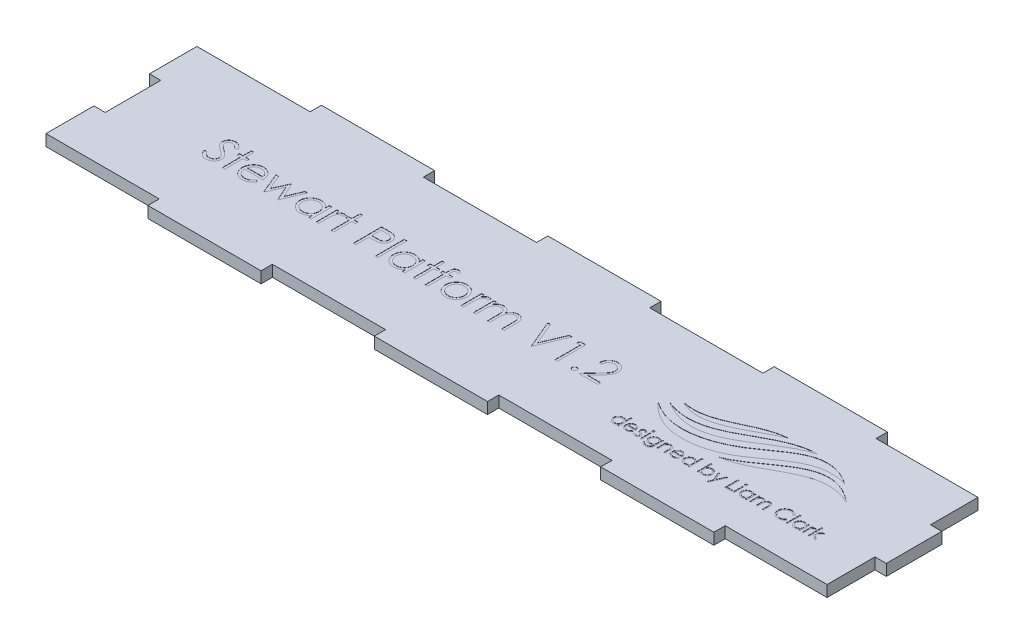
SolidWorks part; units mm, degrees
ref_plane "Front Plane" through (0, 0, 0) normal (0, 0, 1) x (1, 0, 0)
ref_plane "Top Plane" through (0, 0, 0) normal (0, 1, 0) x (1, 0, 0)
ref_plane "Right Plane" through (0, 0, 0) normal (1, 0, 0) x (0, 0, -1)
sketch "Sketch1" plane through (0, 0, 0) normal (0, 1, 0) x (1, 0, 0)
  line L1 (210, -46) -> (-210, -46)
  line L2 (210, -46) -> (210, 46)
  line L3 (210, 46) -> (-210, 46)
  line L4 (-210, -46) -> (-210, 46)
  line L5 (210, -46) -> (-210, 46) construction
  line L6 (210, 46) -> (-210, -46) construction
  point P0 (0, 0)
  dimension "D1" = 92
  dimension "D2" = 420
extrude "Boss-Extrude1" add sketch "Sketch1" along normal blind 6
sketch "Sketch2" plane through (0, 6, 0) normal (0, 1, 0) x (1, 0, 0)
  line L0 (210, 46) -> (-210, 46) construction
  line L1 (-210, 46) -> (-150, 46)
  line L2 (-210, 46) -> (-210, 40)
  line L3 (-210, 40) -> (-150, 40)
  line L4 (-150, 46) -> (-150, 40)
  line L5 (210, 0) -> (-210, 0) construction
  line L6 (-90, 46) -> (-90, 40)
  line L7 (-90, 46) -> (-30, 46)
  line L8 (-30, 46) -> (-30, 40)
  line L9 (-90, 40) -> (-30, 40)
  line L10 (30, 46) -> (30, 40)
  line L11 (30, 46) -> (90, 46)
  line L12 (90, 46) -> (90, 40)
  line L13 (30, 40) -> (90, 40)
  line L14 (-90, -40) -> (-90, -46)
  line L15 (-90, -40) -> (-30, -40)
  line L16 (-30, -40) -> (-30, -46)
  line L17 (-90, -46) -> (-30, -46)
  line L18 (30, -40) -> (30, -46)
  line L19 (30, -40) -> (90, -40)
  line L20 (90, -40) -> (90, -46)
  line L21 (30, -46) -> (90, -46)
  line L22 (-210, -40) -> (-210, -46)
  line L23 (-210, -40) -> (-150, -40)
  line L24 (-150, -40) -> (-150, -46)
  line L25 (-210, -46) -> (-150, -46)
  line L26 (210, -46) -> (210, 46) construction
  line L31 (-210, 46) -> (-210, -46) construction
  line L32 (150, 46) -> (150, 40)
  line L33 (150, 46) -> (210, 46)
  line L34 (210, 46) -> (210, 40)
  line L35 (150, 40) -> (210, 40)
  line L36 (150, -40) -> (150, -46)
  line L37 (150, -40) -> (210, -40)
  line L38 (210, -40) -> (210, -46)
  line L39 (150, -46) -> (210, -46)
  point P6 (-210, 43)
  dimension "D1" = 6
  dimension "D2" = 60
  dimension "D3" = 60
  dimension "D4" = 4
  dimension "D5" = 2
extrude "Cut-Extrude1" cut sketch "Sketch2" against normal through all
sketch "Sketch4" plane through (0, 6, 0) normal (0, 1, 0) x (1, 0, 0)
  line L0 (-210, 40) -> (-210, -40) construction
  line L1 (-210, 14.8279) -> (-204, 14.8279)
  line L2 (-210, 14.8279) -> (-210, -14.6242)
  line L3 (-210, -14.6242) -> (-204, -14.6242)
  line L4 (-204, 14.8279) -> (-204, -14.6242)
  line L5 (210, -40) -> (210, 40) construction
  line L6 (210, 44) -> (204, 44)
  line L7 (210, 44) -> (210, 14.8279)
  line L8 (210, 14.8279) -> (204, 14.8279)
  line L9 (204, 44) -> (204, 14.8279)
  line L10 (210, -44) -> (204, -44)
  line L11 (210, -44) -> (210, -14.6242)
  line L12 (210, -14.6242) -> (204, -14.6242)
  line L13 (204, -44) -> (204, -14.6242)
  dimension "D1" = 6
extrude "Cut-Extrude2" cut sketch "Sketch4" against normal through all
sketch "Sketch6" [suppressed] plane through (0, 6, 0) normal (0, 1, 0) x (1, 0, 0)
  line L0 (-150, -40) -> (-210, -40) construction
  line L14 (-93, -40) -> (-3, -40) construction
  line L15 (-93, -40) -> (-93, -19) construction
  line L16 (-93, -19) -> (-3, -19) construction
  line L17 (-3, -40) -> (-3, -19) construction
  line L18 (7, -40) -> (97, -40) construction
  line L19 (-96, -40) -> (0, -40) construction
  line L20 (-96, -40) -> (-96, -4) construction
  line L21 (-96, -4) -> (0, -4) construction
  line L170 (0, -40) -> (0, -4) construction
  line L171 (7, -40) -> (7, -19) construction
  line L172 (7, -19) -> (97, -19) construction
  line L173 (97, -40) -> (97, -19) construction
  line L174 (4, -40) -> (100, -40) construction
  line L175 (4, -40) -> (4, -4) construction
  line L176 (4, -4) -> (100, -4) construction
  line L177 (100, -40) -> (100, -4) construction
  line L178 (107, -40) -> (197, -40) construction
  line L179 (107, -40) -> (107, -19) construction
  line L180 (107, -19) -> (197, -19) construction
  line L181 (197, -40) -> (197, -19) construction
  line L182 (104, -40) -> (200, -40) construction
  line L183 (104, -40) -> (104, -4) construction
  line L184 (104, -4) -> (200, -4) construction
  line L185 (200, -40) -> (200, -4) construction
  line L188 (204, -14.6242) -> (204, -40) construction
  circle A10 centre (-93, -19) radius 2
  circle A11 centre (-3, -19) radius 2
  circle A12 centre (7, -19) radius 2
  circle A13 centre (97, -19) radius 2
  circle A14 centre (107, -19) radius 2
  circle A15 centre (197, -19) radius 2
  point P12 (-48, -4)
  point P13 (-48, -19)
  dimension "D4" = 96
  dimension "D5" = 36
  dimension "D3" = 4
  dimension "D1" = 90
  dimension "D2" = 21
  dimension "D6" = 3
  dimension "D7" = 4
  dimension "D8" = 4
extrude "Cut-Extrude4" [suppressed] cut sketch "Sketch6" against normal through all
sketch "Sketch7" plane through (0, 6, 0) normal (0, 1, 0) x (1, 0, 0)
  spline S0 degree 3 poles (171.3644, 2.9041) (149.1407, 21.5097) (134.8367, -3.6597) (116.6334, -10.2554) knots 0 0 0 0 1 1 1 1
  spline S1 degree 3 poles (171.3644, 2.9041) (149.4646, 13.3802) (136.0003, -7.5908) (116.6334, -10.2554) knots 0 0 0 0 1 1 1 1
  spline S2 degree 3 poles (162.7253, 10.8278) (143.1108, 16.5369) (123.5303, -12.8755) (86.3571, -14.1609) (75.3762, -0.8054) knots 0 0 0 0 0.516039 1 1 1 1
  spline S3 degree 3 poles (162.7253, 10.8278) (143.6265, 23.6489) (123.0567, -4.3635) (87.9253, -10.4996) (75.3762, -0.8054) knots 0 0 0 0 0.521405 1 1 1 1
  spline S4 degree 3 poles (142.09, 17.4582) (120.5651, 11.5313) (105.0269, -14.3308) (78.5591, 1.9413) knots 0 0 0 0 1 1 1 1
  spline S5 degree 3 poles (142.09, 17.4582) (118.744, 17.2291) (104.4879, -8.4421) (78.5591, 1.9413) knots 0 0 0 0 1 1 1 1
  spline S6 degree 3 poles (126.7097, 16.9429) (113.3406, 11.8174) (97.8584, -2.6356) (82.1577, 5.6639) knots 0 0 0 0 1 1 1 1
  spline S7 degree 3 poles (126.7097, 16.9429) (110.86, 15.9088) (98.9912, 1.6673) (82.1577, 5.6639) knots 0 0 0 0 1 1 1 1
  text T0 "designed by Liam Clark\r\n" font "Century Gothic" height 7
  text T1 "Stewart Platform V1.2" font "Century Gothic" height 15
extrude "Cut-Extrude5" cut sketch "Sketch7" against normal blind 0.1
sketch "Sketch8" [suppressed] plane through (0, 6, 0) normal (0, 1, 0) x (1, 0, 0)
  line L0 (-196, -40) -> (-106, -40) construction
  line L1 (-196, -40) -> (-196, -19) construction
  line L2 (-196, -19) -> (-106, -19) construction
  line L3 (-106, -40) -> (-106, -19) construction
  line L4 (-199, -40) -> (-103, -40) construction
  line L5 (-199, -40) -> (-199, -4) construction
  line L6 (-199, -4) -> (-103, -4) construction
  line L7 (-103, -40) -> (-103, -4) construction
  line L8 (-150, -40) -> (-210, -40) construction
  line L9 (-96, -40) -> (-6, -40) construction
  line L10 (-96, -40) -> (-96, -19) construction
  line L11 (-96, -19) -> (-6, -19) construction
  line L12 (-6, -40) -> (-6, -19) construction
  line L13 (-99, -40) -> (-3, -40) construction
  line L14 (-99, -40) -> (-99, -4) construction
  line L15 (-99, -4) -> (-3, -4) construction
  line L16 (-3, -40) -> (-3, -4) construction
  line L17 (4, -40) -> (94, -40) construction
  line L18 (4, -40) -> (4, -19) construction
  line L19 (4, -19) -> (94, -19) construction
  line L20 (94, -40) -> (94, -19) construction
  line L21 (1, -40) -> (97, -40) construction
  line L22 (1, -40) -> (1, -4) construction
  line L23 (1, -4) -> (97, -4) construction
  line L24 (97, -40) -> (97, -4) construction
  line L25 (-204, -14.6242) -> (-204, 14.8279) construction
  circle A0 centre (-196, -19) radius 2
  circle A1 centre (-106, -19) radius 2
  circle A2 centre (-96, -19) radius 2
  circle A3 centre (-6, -19) radius 2
  circle A4 centre (4, -19) radius 2
  circle A5 centre (94, -19) radius 2
  point P10 (-151, -4)
  point P11 (-151, -19)
  dimension "D3" = 4
  dimension "D1" = 90
  dimension "D2" = 21
  dimension "D4" = 96
  dimension "D5" = 36
  dimension "D7" = 5
  dimension "D8" = 4
  dimension "D6" = 3
extrude "Cut-Extrude6" [suppressed] cut sketch "Sketch8" against normal through all
sketch "Sketch10" [suppressed] plane through (0, 6, 0) normal (0, 1, 0) x (1, 0, 0)
  line L0 (-204, -14.6242) -> (-204, 14.8279) construction
  line L1 (-204, 40) -> (-124, 40) construction
  line L2 (-204, 40) -> (-204, -40) construction
  line L3 (-204, -40) -> (-124, -40) construction
  line L4 (-124, 40) -> (-124, -40) construction
  line L5 (-210, 40) -> (-150, 40) construction
  line L6 (-164, 40) -> (-164, -40) construction
  line L7 (-124, 0) -> (-204, 0) construction
  line L8 (-165, 9.9499) -> (-169.9668, 35.5021)
  line L9 (-200, -36) -> (-128, -36) construction
  line L10 (-200, -36) -> (-200, 36) construction
  line L11 (-200, 36) -> (-128, 36) construction
  line L12 (-128, -36) -> (-128, 36) construction
  line L13 (-200, -36) -> (-128, 36) construction
  line L14 (-200, 36) -> (-128, -36) construction
  line L15 (-163, 9.9499) -> (-158.0332, 35.5021)
  line L16 (-159.2685, 8.8098) -> (-144.9013, 30.5162)
  line L17 (-161.1162, 9.5752) -> (-155.9266, 35.083)
  line L18 (-156.2573, 6.3285) -> (-134.6771, 20.8846)
  line L19 (-157.6715, 7.7427) -> (-143.1154, 29.3229)
  line L20 (-154.4248, 2.8838) -> (-128.917, 8.0734)
  line L21 (-155.1902, 4.7315) -> (-133.4838, 19.0987)
  line L22 (-154.0501, -1) -> (-128.4979, -5.9668)
  line L23 (-154.0501, 1) -> (-128.4979, 5.9668)
  line L24 (-155.1902, -4.7315) -> (-133.4838, -19.0987)
  line L25 (-154.4248, -2.8838) -> (-128.917, -8.0734)
  line L26 (-157.6715, -7.7427) -> (-143.1154, -29.3229)
  line L27 (-156.2573, -6.3285) -> (-134.6771, -20.8846)
  line L28 (-161.1162, -9.5752) -> (-155.9266, -35.083)
  line L29 (-159.2685, -8.8098) -> (-144.9013, -30.5162)
  line L30 (-165, -9.9499) -> (-169.9668, -35.5021)
  line L31 (-163, -9.9499) -> (-158.0332, -35.5021)
  line L32 (-168.7315, -8.8098) -> (-183.0987, -30.5162)
  line L33 (-166.8838, -9.5752) -> (-172.0734, -35.083)
  line L34 (-171.7427, -6.3285) -> (-193.3229, -20.8846)
  line L35 (-170.3285, -7.7427) -> (-184.8846, -29.3229)
  line L36 (-173.5752, -2.8838) -> (-199.083, -8.0734)
  line L37 (-172.8098, -4.7315) -> (-194.5162, -19.0987)
  line L38 (-173.9499, 1) -> (-199.5021, 5.9668)
  line L39 (-173.9499, -1) -> (-199.5021, -5.9668)
  line L40 (-172.8098, 4.7315) -> (-194.5162, 19.0987)
  line L41 (-173.5752, 2.8838) -> (-199.083, 8.0734)
  line L42 (-170.3285, 7.7427) -> (-184.8846, 29.3229)
  line L43 (-171.7427, 6.3285) -> (-193.3229, 20.8846)
  line L44 (-166.8838, 9.5752) -> (-172.0734, 35.083)
  line L45 (-168.7315, 8.8098) -> (-183.0987, 30.5162)
  circle A0 centre (-200, -36) radius 2.25
  circle A1 centre (-128, -36) radius 2.25
  circle A2 centre (-128, 36) radius 2.25
  circle A3 centre (-200, 36) radius 2.25
  arc A5 (-169.9668, 35.5021) -> (-158.0332, 35.5021) centre (-164, 0) cw
  arc A6 (-163, 9.9499) -> (-165, 9.9499) centre (-164, 0) ccw
  arc A7 (-155.9266, 35.083) -> (-144.9013, 30.5162) centre (-164, 0) cw
  arc A8 (-159.2685, 8.8098) -> (-161.1162, 9.5752) centre (-164, 0) ccw
  arc A9 (-143.1154, 29.3229) -> (-134.6771, 20.8846) centre (-164, 0) cw
  arc A10 (-156.2573, 6.3285) -> (-157.6715, 7.7427) centre (-164, 0) ccw
  arc A11 (-133.4838, 19.0987) -> (-128.917, 8.0734) centre (-164, 0) cw
  arc A12 (-154.4248, 2.8838) -> (-155.1902, 4.7315) centre (-164, 0) ccw
  arc A13 (-128.4979, 5.9668) -> (-128.4979, -5.9668) centre (-164, 0) cw
  arc A14 (-154.0501, -1) -> (-154.0501, 1) centre (-164, 0) ccw
  arc A15 (-128.917, -8.0734) -> (-133.4838, -19.0987) centre (-164, 0) cw
  arc A16 (-155.1902, -4.7315) -> (-154.4248, -2.8838) centre (-164, 0) ccw
  arc A17 (-134.6771, -20.8846) -> (-143.1154, -29.3229) centre (-164, 0) cw
  arc A18 (-157.6715, -7.7427) -> (-156.2573, -6.3285) centre (-164, 0) ccw
  arc A19 (-144.9013, -30.5162) -> (-155.9266, -35.083) centre (-164, 0) cw
  arc A20 (-161.1162, -9.5752) -> (-159.2685, -8.8098) centre (-164, 0) ccw
  arc A21 (-158.0332, -35.5021) -> (-169.9668, -35.5021) centre (-164, 0) cw
  arc A22 (-165, -9.9499) -> (-163, -9.9499) centre (-164, 0) ccw
  arc A23 (-172.0734, -35.083) -> (-183.0987, -30.5162) centre (-164, 0) cw
  arc A24 (-168.7315, -8.8098) -> (-166.8838, -9.5752) centre (-164, 0) ccw
  arc A25 (-184.8846, -29.3229) -> (-193.3229, -20.8846) centre (-164, 0) cw
  arc A26 (-171.7427, -6.3285) -> (-170.3285, -7.7427) centre (-164, 0) ccw
  arc A27 (-194.5162, -19.0987) -> (-199.083, -8.0734) centre (-164, 0) cw
  arc A28 (-173.5752, -2.8838) -> (-172.8098, -4.7315) centre (-164, 0) ccw
  arc A29 (-199.5021, -5.9668) -> (-199.5021, 5.9668) centre (-164, 0) cw
  arc A30 (-173.9499, 1) -> (-173.9499, -1) centre (-164, 0) ccw
  arc A31 (-199.083, 8.0734) -> (-194.5162, 19.0987) centre (-164, 0) cw
  arc A32 (-172.8098, 4.7315) -> (-173.5752, 2.8838) centre (-164, 0) ccw
  arc A33 (-193.3229, 20.8846) -> (-184.8846, 29.3229) centre (-164, 0) cw
  arc A34 (-170.3285, 7.7427) -> (-171.7427, 6.3285) centre (-164, 0) ccw
  arc A35 (-183.0987, 30.5162) -> (-172.0734, 35.083) centre (-164, 0) cw
  arc A36 (-166.8838, 9.5752) -> (-168.7315, 8.8098) centre (-164, 0) ccw
  point P12 (-164, 0)
  point P89 (-164, 0)
  dimension "D3" = 4.5
  dimension "D4" = 36
  dimension "D5" = 10
  dimension "D7" = 2
  dimension "D1" = 80
  dimension "D2" = 72
  dimension "D6" = 22
extrude "Cut-Extrude10" [suppressed] cut sketch "Sketch10" against normal through all
mirror "Mirror1" [suppressed] about plane through (0, 0, 0) normal (1, 0, 0)
sketch "Sketch9" [suppressed] plane through (0, 6, 0) normal (0, 1, 0) x (1, 0, 0)
  line L0 (-204, -14.6242) -> (-204, 14.8279) construction
  line L1 (-204, -4) -> (-133, -4) construction
  line L2 (-204, -4) -> (-204, -40) construction
  line L3 (-204, -40) -> (-133, -40) construction
  line L4 (-133, -4) -> (-133, -40) construction
  line L5 (-30, -40) -> (-90, -40) construction
  line L6 (0, 46) -> (0, -46) construction
  line L7 (30, 46) -> (-30, 46) construction
  line L8 (-30, -46) -> (30, -46) construction
  line L9 (204, -4) -> (204, -40) construction
  line L10 (204, -40) -> (133, -40) construction
  line L11 (133, -4) -> (133, -40) construction
  line L12 (204, -4) -> (133, -4) construction
  line L13 (90, -40) -> (30, -40) construction
  line L14 (-107.5, -40) -> (107.5, -40) construction
  line L15 (-107.5, -40) -> (-107.5, 12) construction
  line L16 (-107.5, 12) -> (107.5, 12) construction
  line L17 (107.5, -40) -> (107.5, 12) construction
  line L18 (14, 27) -> (-14, 27) construction
  line L19 (-14, 37) -> (14, 37)
  line L20 (-14, 37) -> (-14, 17)
  line L21 (-14, 17) -> (14, 17)
  line L22 (14, 37) -> (14, 17)
  line L23 (-14, 37) -> (14, 17) construction
  line L24 (-14, 17) -> (14, 37) construction
  line L25 (0, 37) -> (0, 17) construction
  circle A0 centre (82.5, -27) radius 2.25
  circle A1 centre (-34.5, -27) radius 2.25
  circle A2 centre (-20, 27) radius 1.5
  circle A3 centre (20, 27) radius 1.5
  point P24 (0, 12)
  point P30 (0, 27)
  dimension "D4" = 4.5
  dimension "D11" = 3
  dimension "D12" = 40
  dimension "D1" = 71
  dimension "D2" = 36
  dimension "D3" = 215
  dimension "D5" = 52
  dimension "D6" = 25
  dimension "D7" = 117
  dimension "D8" = 13
  dimension "D9" = 28
  dimension "D10" = 20
  dimension "D13" = 5
extrude "Cut-Extrude7" [suppressed] cut sketch "Sketch9" against normal blind 10
sketch "Sketch11" [suppressed] plane through (0, 6, 0) normal (0, 1, 0) x (1, 0, 0)
  line L0 (-204, -14.6242) -> (-204, 14.8279) construction
  line L1 (-194, 30) -> (-190, 30)
  line L2 (-194, 30) -> (-194, 0)
  line L3 (-194, 0) -> (-190, 0)
  line L4 (-190, 30) -> (-190, 0)
  line L5 (-210, 40) -> (-150, 40) construction
  line L6 (-186.1633, 30.0024) -> (-186.1633, 0.0024)
  line L7 (-186.1633, 30.0024) -> (-182.1633, 30.0024)
  line L8 (-182.1633, 30.0024) -> (-182.1633, 0.0024)
  line L9 (-186.1633, 0.0024) -> (-182.1633, 0.0024)
  line L10 (-178.3265, 30.0049) -> (-178.3265, 0.0049)
  line L11 (-178.3265, 30.0049) -> (-174.3265, 30.0049)
  line L12 (-174.3265, 30.0049) -> (-174.3265, 0.0049)
  line L13 (-178.3265, 0.0049) -> (-174.3265, 0.0049)
  line L14 (-170.4898, 30.0073) -> (-170.4898, 0.0073)
  line L15 (-170.4898, 30.0073) -> (-166.4898, 30.0073)
  line L16 (-166.4898, 30.0073) -> (-166.4898, 0.0073)
  line L17 (-170.4898, 0.0073) -> (-166.4898, 0.0073)
  line L18 (-162.6531, 30.0097) -> (-162.6531, 0.0097)
  line L19 (-162.6531, 30.0097) -> (-158.6531, 30.0097)
  line L20 (-158.6531, 30.0097) -> (-158.6531, 0.0097)
  line L21 (-162.6531, 0.0097) -> (-158.6531, 0.0097)
  line L22 (-154.8163, 30.0122) -> (-154.8163, 0.0122)
  line L23 (-154.8163, 30.0122) -> (-150.8163, 30.0122)
  line L24 (-150.8163, 30.0122) -> (-150.8163, 0.0122)
  line L25 (-154.8163, 0.0122) -> (-150.8163, 0.0122)
  line L26 (-146.9796, 30.0146) -> (-146.9796, 0.0146)
  line L27 (-146.9796, 30.0146) -> (-142.9796, 30.0146)
  line L28 (-142.9796, 30.0146) -> (-142.9796, 0.0146)
  line L29 (-146.9796, 0.0146) -> (-142.9796, 0.0146)
  line L30 (-139.1429, 30.017) -> (-139.1429, 0.017)
  line L31 (-139.1429, 30.017) -> (-135.1429, 30.017)
  line L32 (-135.1429, 30.017) -> (-135.1429, 0.017)
  line L33 (-139.1429, 0.017) -> (-135.1429, 0.017)
  line L34 (-131.3061, 30.0195) -> (-131.3061, 0.0195)
  line L35 (-131.3061, 30.0195) -> (-127.3061, 30.0195)
  line L36 (-127.3061, 30.0195) -> (-127.3061, 0.0195)
  line L37 (-131.3061, 0.0195) -> (-127.3061, 0.0195)
  line L38 (-123.4694, 30.0219) -> (-123.4694, 0.0219)
  line L39 (-123.4694, 30.0219) -> (-119.4694, 30.0219)
  line L40 (-119.4694, 30.0219) -> (-119.4694, 0.0219)
  line L41 (-123.4694, 0.0219) -> (-119.4694, 0.0219)
  line L42 (-115.6327, 30.0243) -> (-115.6327, 0.0243)
  line L43 (-115.6327, 30.0243) -> (-111.6327, 30.0243)
  line L44 (-111.6327, 30.0243) -> (-111.6327, 0.0243)
  line L45 (-115.6327, 0.0243) -> (-111.6327, 0.0243)
  line L46 (-107.7959, 30.0268) -> (-107.7959, 0.0268)
  line L47 (-107.7959, 30.0268) -> (-103.7959, 30.0268)
  line L48 (-103.7959, 30.0268) -> (-103.7959, 0.0268)
  line L49 (-107.7959, 0.0268) -> (-103.7959, 0.0268)
  line L50 (-99.9592, 30.0292) -> (-99.9592, 0.0292)
  line L51 (-99.9592, 30.0292) -> (-95.9592, 30.0292)
  line L52 (-95.9592, 30.0292) -> (-95.9592, 0.0292)
  line L53 (-99.9592, 0.0292) -> (-95.9592, 0.0292)
  line L54 (-92.1224, 30.0316) -> (-92.1224, 0.0316)
  line L55 (-92.1224, 30.0316) -> (-88.1224, 30.0316)
  line L56 (-88.1224, 30.0316) -> (-88.1224, 0.0316)
  line L57 (-92.1224, 0.0316) -> (-88.1224, 0.0316)
  line L58 (-84.2857, 30.0341) -> (-84.2857, 0.0341)
  line L59 (-84.2857, 30.0341) -> (-80.2857, 30.0341)
  line L60 (-80.2857, 30.0341) -> (-80.2857, 0.0341)
  line L61 (-84.2857, 0.0341) -> (-80.2857, 0.0341)
  line L62 (-76.449, 30.0365) -> (-76.449, 0.0365)
  line L63 (-76.449, 30.0365) -> (-72.449, 30.0365)
  line L64 (-72.449, 30.0365) -> (-72.449, 0.0365)
  line L65 (-76.449, 0.0365) -> (-72.449, 0.0365)
  line L66 (-68.6122, 30.039) -> (-68.6122, 0.039)
  line L67 (-68.6122, 30.039) -> (-64.6122, 30.039)
  line L68 (-64.6122, 30.039) -> (-64.6122, 0.039)
  line L69 (-68.6122, 0.039) -> (-64.6122, 0.039)
  line L70 (-60.7755, 30.0414) -> (-60.7755, 0.0414)
  line L71 (-60.7755, 30.0414) -> (-56.7755, 30.0414)
  line L72 (-56.7755, 30.0414) -> (-56.7755, 0.0414)
  line L73 (-60.7755, 0.0414) -> (-56.7755, 0.0414)
  line L74 (-52.9388, 30.0438) -> (-52.9388, 0.0438)
  line L75 (-52.9388, 30.0438) -> (-48.9388, 30.0438)
  line L76 (-48.9388, 30.0438) -> (-48.9388, 0.0438)
  line L77 (-52.9388, 0.0438) -> (-48.9388, 0.0438)
  line L78 (-45.102, 30.0463) -> (-45.102, 0.0463)
  line L79 (-45.102, 30.0463) -> (-41.102, 30.0463)
  line L80 (-41.102, 30.0463) -> (-41.102, 0.0463)
  line L81 (-45.102, 0.0463) -> (-41.102, 0.0463)
  line L82 (-37.2653, 30.0487) -> (-37.2653, 0.0487)
  line L83 (-37.2653, 30.0487) -> (-33.2653, 30.0487)
  line L84 (-33.2653, 30.0487) -> (-33.2653, 0.0487)
  line L85 (-37.2653, 0.0487) -> (-33.2653, 0.0487)
  line L86 (-29.4286, 30.0511) -> (-29.4286, 0.0511)
  line L87 (-29.4286, 30.0511) -> (-25.4286, 30.0511)
  line L88 (-25.4286, 30.0511) -> (-25.4286, 0.0511)
  line L89 (-29.4286, 0.0511) -> (-25.4286, 0.0511)
  line L90 (-21.5918, 30.0536) -> (-21.5918, 0.0536)
  line L91 (-21.5918, 30.0536) -> (-17.5918, 30.0536)
  line L92 (-17.5918, 30.0536) -> (-17.5918, 0.0536)
  line L93 (-21.5918, 0.0536) -> (-17.5918, 0.0536)
  line L94 (-13.7551, 30.056) -> (-13.7551, 0.056)
  line L95 (-13.7551, 30.056) -> (-9.7551, 30.056)
  line L96 (-9.7551, 30.056) -> (-9.7551, 0.056)
  line L97 (-13.7551, 0.056) -> (-9.7551, 0.056)
  line L98 (-5.9184, 30.0584) -> (-5.9184, 0.0584)
  line L99 (-5.9184, 30.0584) -> (-1.9184, 30.0584)
  line L100 (-1.9184, 30.0584) -> (-1.9184, 0.0584)
  line L101 (-5.9184, 0.0584) -> (-1.9184, 0.0584)
  line L102 (1.9184, 30.0609) -> (1.9184, 0.0609)
  line L103 (1.9184, 30.0609) -> (5.9184, 30.0609)
  line L104 (5.9184, 30.0609) -> (5.9184, 0.0609)
  line L105 (1.9184, 0.0609) -> (5.9184, 0.0609)
  line L106 (9.7551, 30.0633) -> (9.7551, 0.0633)
  line L107 (9.7551, 30.0633) -> (13.7551, 30.0633)
  line L108 (13.7551, 30.0633) -> (13.7551, 0.0633)
  line L109 (9.7551, 0.0633) -> (13.7551, 0.0633)
  line L110 (17.5918, 30.0657) -> (17.5918, 0.0657)
  line L111 (17.5918, 30.0657) -> (21.5918, 30.0657)
  line L112 (21.5918, 30.0657) -> (21.5918, 0.0657)
  line L113 (17.5918, 0.0657) -> (21.5918, 0.0657)
  line L114 (25.4286, 30.0682) -> (25.4286, 0.0682)
  line L115 (25.4286, 30.0682) -> (29.4286, 30.0682)
  line L116 (29.4286, 30.0682) -> (29.4286, 0.0682)
  line L117 (25.4286, 0.0682) -> (29.4286, 0.0682)
  line L118 (33.2653, 30.0706) -> (33.2653, 0.0706)
  line L119 (33.2653, 30.0706) -> (37.2653, 30.0706)
  line L120 (37.2653, 30.0706) -> (37.2653, 0.0706)
  line L121 (33.2653, 0.0706) -> (37.2653, 0.0706)
  line L122 (41.102, 30.073) -> (41.102, 0.073)
  line L123 (41.102, 30.073) -> (45.102, 30.073)
  line L124 (45.102, 30.073) -> (45.102, 0.073)
  line L125 (41.102, 0.073) -> (45.102, 0.073)
  line L126 (48.9388, 30.0755) -> (48.9388, 0.0755)
  line L127 (48.9388, 30.0755) -> (52.9388, 30.0755)
  line L128 (52.9388, 30.0755) -> (52.9388, 0.0755)
  line L129 (48.9388, 0.0755) -> (52.9388, 0.0755)
  line L130 (56.7755, 30.0779) -> (56.7755, 0.0779)
  line L131 (56.7755, 30.0779) -> (60.7755, 30.0779)
  line L132 (60.7755, 30.0779) -> (60.7755, 0.0779)
  line L133 (56.7755, 0.0779) -> (60.7755, 0.0779)
  line L134 (64.6122, 30.0803) -> (64.6122, 0.0803)
  line L135 (64.6122, 30.0803) -> (68.6122, 30.0803)
  line L136 (68.6122, 30.0803) -> (68.6122, 0.0803)
  line L137 (64.6122, 0.0803) -> (68.6122, 0.0803)
  line L138 (72.449, 30.0828) -> (72.449, 0.0828)
  line L139 (72.449, 30.0828) -> (76.449, 30.0828)
  line L140 (76.449, 30.0828) -> (76.449, 0.0828)
  line L141 (72.449, 0.0828) -> (76.449, 0.0828)
  line L142 (80.2857, 30.0852) -> (80.2857, 0.0852)
  line L143 (80.2857, 30.0852) -> (84.2857, 30.0852)
  line L144 (84.2857, 30.0852) -> (84.2857, 0.0852)
  line L145 (80.2857, 0.0852) -> (84.2857, 0.0852)
  line L146 (88.1224, 30.0876) -> (88.1224, 0.0876)
  line L147 (88.1224, 30.0876) -> (92.1224, 30.0876)
  line L148 (92.1224, 30.0876) -> (92.1224, 0.0876)
  line L149 (88.1224, 0.0876) -> (92.1224, 0.0876)
  line L150 (95.9592, 30.0901) -> (95.9592, 0.0901)
  line L151 (95.9592, 30.0901) -> (99.9592, 30.0901)
  line L152 (99.9592, 30.0901) -> (99.9592, 0.0901)
  line L153 (95.9592, 0.0901) -> (99.9592, 0.0901)
  line L154 (103.7959, 30.0925) -> (103.7959, 0.0925)
  line L155 (103.7959, 30.0925) -> (107.7959, 30.0925)
  line L156 (107.7959, 30.0925) -> (107.7959, 0.0925)
  line L157 (103.7959, 0.0925) -> (107.7959, 0.0925)
  line L158 (111.6327, 30.0949) -> (111.6327, 0.0949)
  line L159 (111.6327, 30.0949) -> (115.6327, 30.0949)
  line L160 (115.6327, 30.0949) -> (115.6327, 0.0949)
  line L161 (111.6327, 0.0949) -> (115.6327, 0.0949)
  line L162 (119.4694, 30.0974) -> (119.4694, 0.0974)
  line L163 (119.4694, 30.0974) -> (123.4694, 30.0974)
  line L164 (123.4694, 30.0974) -> (123.4694, 0.0974)
  line L165 (119.4694, 0.0974) -> (123.4694, 0.0974)
  line L166 (127.3061, 30.0998) -> (127.3061, 0.0998)
  line L167 (127.3061, 30.0998) -> (131.3061, 30.0998)
  line L168 (131.3061, 30.0998) -> (131.3061, 0.0998)
  line L169 (127.3061, 0.0998) -> (131.3061, 0.0998)
  line L170 (135.1429, 30.1023) -> (135.1429, 0.1023)
  line L171 (135.1429, 30.1023) -> (139.1429, 30.1023)
  line L172 (139.1429, 30.1023) -> (139.1429, 0.1023)
  line L173 (135.1429, 0.1023) -> (139.1429, 0.1023)
  line L174 (142.9796, 30.1047) -> (142.9796, 0.1047)
  line L175 (142.9796, 30.1047) -> (146.9796, 30.1047)
  line L176 (146.9796, 30.1047) -> (146.9796, 0.1047)
  line L177 (142.9796, 0.1047) -> (146.9796, 0.1047)
  line L178 (150.8163, 30.1071) -> (150.8163, 0.1071)
  line L179 (150.8163, 30.1071) -> (154.8163, 30.1071)
  line L180 (154.8163, 30.1071) -> (154.8163, 0.1071)
  line L181 (150.8163, 0.1071) -> (154.8163, 0.1071)
  line L182 (158.6531, 30.1096) -> (158.6531, 0.1096)
  line L183 (158.6531, 30.1096) -> (162.6531, 30.1096)
  line L184 (162.6531, 30.1096) -> (162.6531, 0.1096)
  line L185 (158.6531, 0.1096) -> (162.6531, 0.1096)
  line L186 (166.4898, 30.112) -> (166.4898, 0.112)
  line L187 (166.4898, 30.112) -> (170.4898, 30.112)
  line L188 (170.4898, 30.112) -> (170.4898, 0.112)
  line L189 (166.4898, 0.112) -> (170.4898, 0.112)
  line L190 (174.3265, 30.1144) -> (174.3265, 0.1144)
  line L191 (174.3265, 30.1144) -> (178.3265, 30.1144)
  line L192 (178.3265, 30.1144) -> (178.3265, 0.1144)
  line L193 (174.3265, 0.1144) -> (178.3265, 0.1144)
  line L194 (182.1633, 30.1169) -> (182.1633, 0.1169)
  line L195 (182.1633, 30.1169) -> (186.1633, 30.1169)
  line L196 (186.1633, 30.1169) -> (186.1633, 0.1169)
  line L197 (182.1633, 0.1169) -> (186.1633, 0.1169)
  line L198 (190, 30.1193) -> (190, 0.1193)
  line L199 (190, 30.1193) -> (194, 30.1193)
  line L200 (194, 30.1193) -> (194, 0.1193)
  line L201 (190, 0.1193) -> (194, 0.1193)
  line L202 (204, 40) -> (204, 14.8279) construction
  dimension "D1" = 30
  dimension "D2" = 4
  dimension "D3" = 10
  dimension "D4" = 10
  dimension "D6" = 10
  dimension "D5" = 50
extrude "Cut-Extrude11" [suppressed] cut sketch "Sketch11" against normal blind 10
sketch "Sketch12" [suppressed] plane through (0, 6, 0) normal (0, 1, 0) x (1, 0, 0)
  line L0 (-90, 40) -> (-30, 40) construction
  line L1 (-75, 30) -> (-45, 30)
  line L2 (-75, 30) -> (-75, 18)
  line L3 (-75, 18) -> (-45, 18)
  line L4 (-45, 30) -> (-45, 18)
  point P6 (-60, 40)
  point P7 (-60, 30)
  dimension "D1" = 12
  dimension "D2" = 30
  dimension "D3" = 10
extrude "Cut-Extrude12" [suppressed] cut sketch "Sketch12" against normal blind 10
fillet "Fillet1" [suppressed] radius 5
sketch "Sketch13" [suppressed] plane through (0, 6, 0) normal (0, 1, 0) x (1, 0, 0)
  line L0 (30, 40) -> (90, 40) construction
  line L1 (50, 30) -> (70, 30)
  line L2 (50, 30) -> (50, 20)
  line L3 (50, 20) -> (70, 20)
  line L4 (70, 30) -> (70, 20)
  point P4 (60, 30)
  point P7 (60, 40)
  dimension "D1" = 10
  dimension "D2" = 20
  dimension "D3" = 10
extrude "Cut-Extrude13" [suppressed] cut sketch "Sketch13" against normal through all
fillet "Fillet2" [suppressed] radius 2
